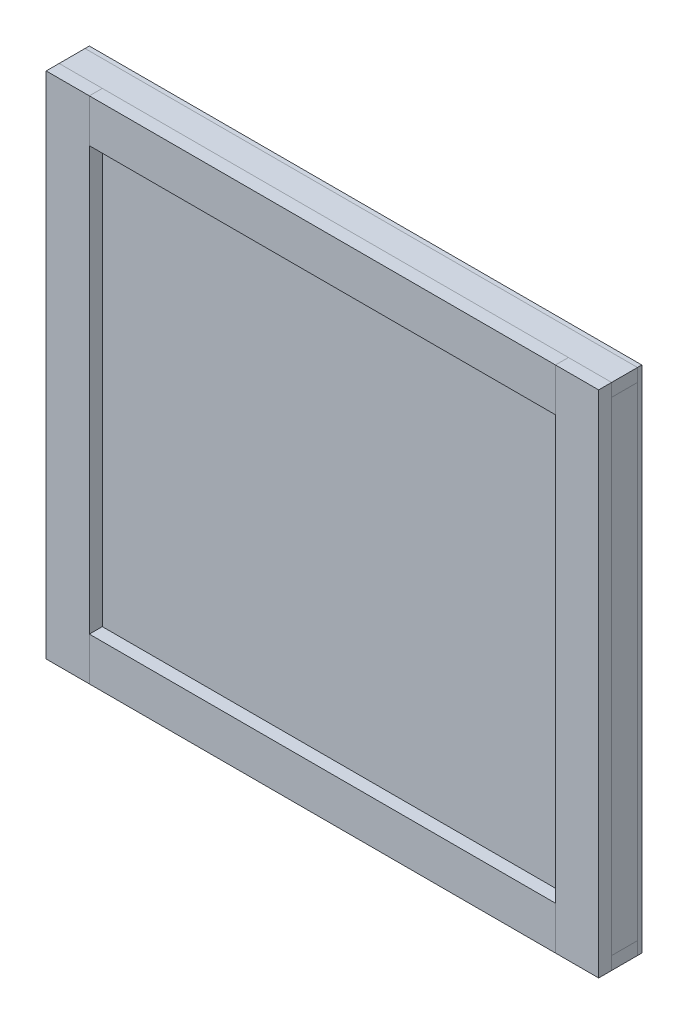
SolidWorks part; units mm, degrees
ref_plane "Front" through (0, 0, 0) normal (0, 0, 1) x (1, 0, 0)
ref_plane "Top" through (0, 0, 0) normal (0, 1, 0) x (1, 0, 0)
ref_plane "Right" through (0, 0, 0) normal (1, 0, 0) x (0, 0, -1)
sketch "Sketch1" plane through (0, 0, 0) normal (0, 0, 1) x (1, 0, 0)
  line L1 (406.4, -374.65) -> (-406.4, -374.65)
  line L2 (406.4, -374.65) -> (406.4, 374.65)
  line L3 (406.4, 374.65) -> (-406.4, 374.65)
  line L4 (-406.4, -374.65) -> (-406.4, 374.65)
  line L5 (406.4, -374.65) -> (-406.4, 374.65) construction
  line L6 (406.4, 374.65) -> (-406.4, -374.65) construction
  point P0 (0, 0)
  dimension "D1" = 812.8
  dimension "D2" = 749.3
extrude "Boss-Extrude1" add sketch "Sketch1" along normal blind 6.35
sketch "Sketch2" plane through (0, 0, 6.35) normal (0, 0, 1) x (1, 0, 0)
  line L0 (406.4, -374.65) -> (406.4, 374.65) construction
  line L1 (-406.4, 374.65) -> (406.4, 374.65)
  line L2 (-406.4, 374.65) -> (-406.4, 355.6)
  line L3 (-406.4, 355.6) -> (406.4, 355.6)
  line L4 (406.4, 374.65) -> (406.4, 355.6)
  line L6 (-406.4, -374.65) -> (406.4, -374.65)
  line L7 (-406.4, -374.65) -> (-406.4, -355.6)
  line L8 (-406.4, -355.6) -> (406.4, -355.6)
  line L9 (406.4, -374.65) -> (406.4, -355.6)
  line L10 (-406.4, 355.6) -> (-387.35, 355.6)
  line L11 (-406.4, 355.6) -> (-406.4, -355.6)
  line L12 (-406.4, -355.6) -> (-387.35, -355.6)
  line L13 (-387.35, 355.6) -> (-387.35, -355.6)
  line L14 (406.4, 355.6) -> (387.35, 355.6)
  line L15 (406.4, 355.6) -> (406.4, -355.6)
  line L16 (406.4, -355.6) -> (387.35, -355.6)
  line L17 (387.35, 355.6) -> (387.35, -355.6)
  line M14 (-406.4, 374.65) -> (-406.4, -374.65)
  line M15 (-406.4, -374.65) -> (406.4, -374.65)
  line M16 (406.4, -374.65) -> (406.4, 374.65)
  line M17 (406.4, 374.65) -> (-406.4, 374.65)
  dimension "D1" = 19.05
  dimension "D2" = 19.05
  dimension "D3" = 19.05
extrude "Boss-Extrude2" add sketch "Sketch2" along normal blind 38.1 separate body contours L8 M14 M15 M16 | L3 M14 M16 M17 region at (0, 365.125, 6.35) region at (0, -365.125, 6.35)
extrude "Boss-Extrude3" add sketch "Sketch2<3>" along normal blind 38.1 separate body contours L13 L3 L8 M14 | L3 L17 L8 M16 region at (-396.875, 0, 6.35) region at (396.875, 0, 6.35)
sketch "Sketch2<3>" plane through (0, 0, 6.35) normal (0, 0, 1) x (1, 0, 0) same geometry as "Sketch2"
sketch "Sketch3" plane through (0, 0, 44.45) normal (0, 0, 1) x (1, 0, 0)
  line L0 (-406.4, -374.65) -> (406.4, -374.65) construction
  line L1 (-406.4, 374.65) -> (-342.9, 374.65)
  line L2 (-406.4, 374.65) -> (-406.4, -374.65)
  line L3 (-406.4, -374.65) -> (-342.9, -374.65)
  line L4 (-342.9, 374.65) -> (-342.9, -374.65)
  line L5 (406.4, 374.65) -> (-406.4, 374.65) construction
  line L6 (406.4, -374.65) -> (342.9, -374.65)
  line L7 (406.4, -374.65) -> (406.4, 374.65)
  line L8 (406.4, 374.65) -> (342.9, 374.65)
  line L9 (342.9, -374.65) -> (342.9, 374.65)
  line L11 (-342.9, 374.65) -> (342.9, 374.65)
  line L12 (-342.9, 374.65) -> (-342.9, 311.15)
  line L13 (-342.9, 311.15) -> (342.9, 311.15)
  line L14 (342.9, 374.65) -> (342.9, 311.15)
  line L15 (-342.9, -374.65) -> (342.9, -374.65)
  line L16 (-342.9, -374.65) -> (-342.9, -311.15)
  line L17 (-342.9, -311.15) -> (342.9, -311.15)
  line L18 (342.9, -374.65) -> (342.9, -311.15)
  line M10 (-406.4, 374.65) -> (-406.4, 355.6)
  line M11 (-406.4, 355.6) -> (406.4, 355.6)
  line M12 (406.4, 355.6) -> (406.4, 374.65)
  line M13 (406.4, 374.65) -> (-406.4, 374.65)
  dimension "D1" = 63.5
  dimension "D2" = 63.5
  dimension "D3" = 63.5
extrude "Boss-Extrude4" add sketch "Sketch3" along normal blind 19.05 separate body contours L4 L2 L3 M11 | L9 L6 L7 M11 | L4 M13 M10 M11 | L9 M11 M12 M13 region at (-374.65, 365.125, 44.45) region at (-374.65, -9.525, 44.45) region at (374.65, 365.125, 44.45) region at (374.65, -9.525, 44.45)
extrude "Boss-Extrude5" add sketch "Sketch3<3>" along normal blind 19.05 separate body contours L17 L4 L15 L9 | L4 L13 L9 M11 | L9 L4 M11 M13 region at (0, 365.125, 44.45) region at (0, 333.375, 44.45) region at (0, -342.9, 44.45)
sketch "Sketch3<3>" plane through (0, 0, 44.45) normal (0, 0, 1) x (1, 0, 0) same geometry as "Sketch3"
